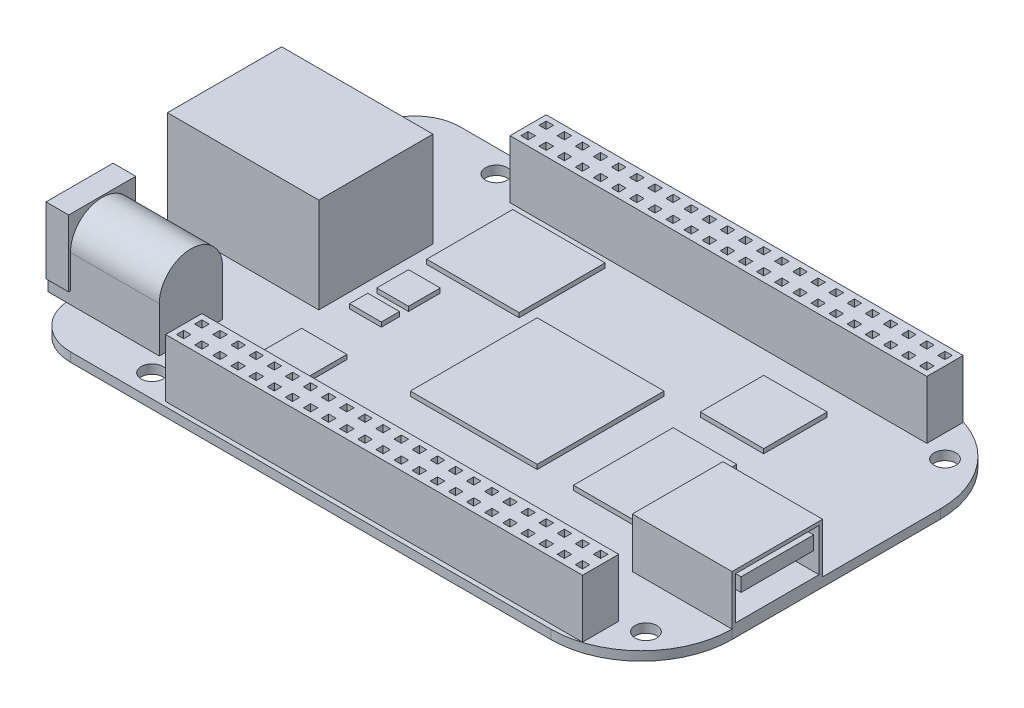
SolidWorks part; units mm, degrees
material "ABS"
ref_plane "Front Plane" through (0, 0, 0) normal (0, 0, 1) x (1, 0, 0)
ref_plane "Top Plane" through (0, 0, 0) normal (0, 1, 0) x (1, 0, 0)
ref_plane "Right Plane" through (0, 0, 0) normal (1, 0, 0) x (0, 0, -1)
sketch "Sketch1" plane through (0, 0, 0) normal (0, 1, 0) x (1, 0, 0)
  line L1 (-12.7, 0) -> (-80.01, 0)
  line L2 (0, 12.7) -> (0, 41.91)
  line L3 (-12.7, 54.61) -> (-80.01, 54.61)
  line L4 (-86.36, 6.35) -> (-86.36, 48.26)
  arc A0 (0, 12.7) -> (-12.7, 0) centre (-12.7, 12.7) cw
  arc A1 (0, 41.91) -> (-12.7, 54.61) centre (-12.7, 41.91) ccw
  arc A2 (-86.36, 6.35) -> (-80.01, 0) centre (-80.01, 6.35) ccw
  arc A3 (-86.36, 48.26) -> (-80.01, 54.61) centre (-80.01, 48.26) cw
  point P7 (0, 0)
  point P10 (0, 54.61)
  point P13 (-86.36, 0)
  dimension "D3" = 12.7
  dimension "D4" = 6.35
  dimension "D1" = 86.36
  dimension "D2" = 54.61
extrude "Boss-Extrude1" add sketch "Sketch1" along normal blind 1.27
sketch "Sketch2" plane through (0, 1.27, 0) normal (0, 1, 0) x (1, 0, 0)
  line L0 (-80.01, 0) -> (-12.7, 0) construction
  line L2 (-71.755, 51.435) -> (-71.755, 3.175) construction
  line L3 (-86.36, 48.26) -> (-86.36, 6.35) construction
  line L4 (-5.715, 48.26) -> (-5.715, 6.35) construction
  circle A0 centre (-71.755, 51.435) radius 1.524
  circle A1 centre (-71.755, 3.175) radius 1.524
  circle A2 centre (-5.715, 48.26) radius 1.524
  circle A3 centre (-5.715, 6.35) radius 1.524
  dimension "D7" = 3.048
  dimension "D1" = 48.26
  dimension "D2" = 41.91
  dimension "D3" = 6.35
  dimension "D4" = 14.605
  dimension "D5" = 80.645
  dimension "D6" = 3.175
extrude "Cut-Extrude1" cut sketch "Sketch2" along direction (0, -1, 0) on the side against the normal up to surface (1.27 mm away) up to face at (-44.4387, 0, -27.305)
sketch "Sketch3" plane through (0, 1.27, 0) normal (0, 1, 0) x (1, 0, 0)
  line L0 (-10.16, 48.895) -> (-10.16, 50.165) construction
  line L1 (-67.31, 53.975) -> (-8.89, 53.975)
  line L2 (-67.31, 53.975) -> (-67.31, 48.895)
  line L3 (-67.31, 48.895) -> (-8.89, 48.895)
  line L4 (-8.89, 53.975) -> (-8.89, 48.895)
  line L5 (-86.36, 27.305) -> (0, 27.305) construction
  line L6 (0, 12.7) -> (0, 41.91) construction
  line L7 (-66.548, 4.953) -> (-66.548, 3.937)
  line L8 (-66.548, 4.953) -> (-65.532, 4.953)
  line L9 (-10.16, 50.165) -> (-10.16, 52.705) construction
  line L10 (-10.16, 52.705) -> (-10.16, 53.975) construction
  line L11 (-13.208, 52.197) -> (-12.192, 52.197)
  line L12 (-10.668, 53.213) -> (-9.652, 53.213)
  line L13 (-10.668, 53.213) -> (-10.668, 52.197)
  line L14 (-10.668, 52.197) -> (-9.652, 52.197)
  line L15 (-9.652, 53.213) -> (-9.652, 52.197)
  line L16 (-10.668, 53.213) -> (-9.652, 52.197) construction
  line L17 (-10.668, 52.197) -> (-9.652, 53.213) construction
  line L18 (-10.668, 49.657) -> (-9.652, 49.657)
  line L19 (-10.668, 49.657) -> (-10.668, 50.673)
  line L20 (-10.668, 50.673) -> (-9.652, 50.673)
  line L21 (-9.652, 49.657) -> (-9.652, 50.673)
  line L22 (-10.668, 49.657) -> (-9.652, 50.673) construction
  line L23 (-10.668, 50.673) -> (-9.652, 49.657) construction
  line L24 (-13.208, 53.213) -> (-13.208, 52.197)
  line L25 (-13.208, 53.213) -> (-12.192, 53.213)
  line L26 (-12.192, 53.213) -> (-12.192, 52.197)
  line L27 (-13.208, 50.673) -> (-12.192, 50.673)
  line L28 (-12.192, 49.657) -> (-12.192, 50.673)
  line L29 (-13.208, 49.657) -> (-12.192, 49.657)
  line L30 (-13.208, 49.657) -> (-13.208, 50.673)
  line L31 (-15.748, 52.197) -> (-14.732, 52.197)
  line L32 (-15.748, 53.213) -> (-15.748, 52.197)
  line L33 (-15.748, 53.213) -> (-14.732, 53.213)
  line L34 (-14.732, 53.213) -> (-14.732, 52.197)
  line L35 (-15.748, 50.673) -> (-14.732, 50.673)
  line L36 (-14.732, 49.657) -> (-14.732, 50.673)
  line L37 (-15.748, 49.657) -> (-14.732, 49.657)
  line L38 (-15.748, 49.657) -> (-15.748, 50.673)
  line L39 (-18.288, 52.197) -> (-17.272, 52.197)
  line L40 (-18.288, 53.213) -> (-18.288, 52.197)
  line L41 (-18.288, 53.213) -> (-17.272, 53.213)
  line L42 (-17.272, 53.213) -> (-17.272, 52.197)
  line L43 (-18.288, 50.673) -> (-17.272, 50.673)
  line L44 (-17.272, 49.657) -> (-17.272, 50.673)
  line L45 (-18.288, 49.657) -> (-17.272, 49.657)
  line L46 (-18.288, 49.657) -> (-18.288, 50.673)
  line L47 (-20.828, 52.197) -> (-19.812, 52.197)
  line L48 (-20.828, 53.213) -> (-20.828, 52.197)
  line L49 (-20.828, 53.213) -> (-19.812, 53.213)
  line L50 (-19.812, 53.213) -> (-19.812, 52.197)
  line L51 (-20.828, 50.673) -> (-19.812, 50.673)
  line L52 (-19.812, 49.657) -> (-19.812, 50.673)
  line L53 (-20.828, 49.657) -> (-19.812, 49.657)
  line L54 (-20.828, 49.657) -> (-20.828, 50.673)
  line L55 (-23.368, 52.197) -> (-22.352, 52.197)
  line L56 (-23.368, 53.213) -> (-23.368, 52.197)
  line L57 (-23.368, 53.213) -> (-22.352, 53.213)
  line L58 (-22.352, 53.213) -> (-22.352, 52.197)
  line L59 (-23.368, 50.673) -> (-22.352, 50.673)
  line L60 (-22.352, 49.657) -> (-22.352, 50.673)
  line L61 (-23.368, 49.657) -> (-22.352, 49.657)
  line L62 (-23.368, 49.657) -> (-23.368, 50.673)
  line L63 (-25.908, 52.197) -> (-24.892, 52.197)
  line L64 (-25.908, 53.213) -> (-25.908, 52.197)
  line L65 (-25.908, 53.213) -> (-24.892, 53.213)
  line L66 (-24.892, 53.213) -> (-24.892, 52.197)
  line L67 (-25.908, 50.673) -> (-24.892, 50.673)
  line L68 (-24.892, 49.657) -> (-24.892, 50.673)
  line L69 (-25.908, 49.657) -> (-24.892, 49.657)
  line L70 (-25.908, 49.657) -> (-25.908, 50.673)
  line L71 (-28.448, 52.197) -> (-27.432, 52.197)
  line L72 (-28.448, 53.213) -> (-28.448, 52.197)
  line L73 (-28.448, 53.213) -> (-27.432, 53.213)
  line L74 (-27.432, 53.213) -> (-27.432, 52.197)
  line L75 (-28.448, 50.673) -> (-27.432, 50.673)
  line L76 (-27.432, 49.657) -> (-27.432, 50.673)
  line L77 (-28.448, 49.657) -> (-27.432, 49.657)
  line L78 (-28.448, 49.657) -> (-28.448, 50.673)
  line L79 (-30.988, 52.197) -> (-29.972, 52.197)
  line L80 (-30.988, 53.213) -> (-30.988, 52.197)
  line L81 (-30.988, 53.213) -> (-29.972, 53.213)
  line L82 (-29.972, 53.213) -> (-29.972, 52.197)
  line L83 (-30.988, 50.673) -> (-29.972, 50.673)
  line L84 (-29.972, 49.657) -> (-29.972, 50.673)
  line L85 (-30.988, 49.657) -> (-29.972, 49.657)
  line L86 (-30.988, 49.657) -> (-30.988, 50.673)
  line L87 (-33.528, 52.197) -> (-32.512, 52.197)
  line L88 (-33.528, 53.213) -> (-33.528, 52.197)
  line L89 (-33.528, 53.213) -> (-32.512, 53.213)
  line L90 (-32.512, 53.213) -> (-32.512, 52.197)
  line L91 (-33.528, 50.673) -> (-32.512, 50.673)
  line L92 (-32.512, 49.657) -> (-32.512, 50.673)
  line L93 (-33.528, 49.657) -> (-32.512, 49.657)
  line L94 (-33.528, 49.657) -> (-33.528, 50.673)
  line L95 (-36.068, 52.197) -> (-35.052, 52.197)
  line L96 (-36.068, 53.213) -> (-36.068, 52.197)
  line L97 (-36.068, 53.213) -> (-35.052, 53.213)
  line L98 (-35.052, 53.213) -> (-35.052, 52.197)
  line L99 (-36.068, 50.673) -> (-35.052, 50.673)
  line L100 (-35.052, 49.657) -> (-35.052, 50.673)
  line L101 (-36.068, 49.657) -> (-35.052, 49.657)
  line L102 (-36.068, 49.657) -> (-36.068, 50.673)
  line L103 (-38.608, 52.197) -> (-37.592, 52.197)
  line L104 (-38.608, 53.213) -> (-38.608, 52.197)
  line L105 (-38.608, 53.213) -> (-37.592, 53.213)
  line L106 (-37.592, 53.213) -> (-37.592, 52.197)
  line L107 (-38.608, 50.673) -> (-37.592, 50.673)
  line L108 (-37.592, 49.657) -> (-37.592, 50.673)
  line L109 (-38.608, 49.657) -> (-37.592, 49.657)
  line L110 (-38.608, 49.657) -> (-38.608, 50.673)
  line L111 (-41.148, 52.197) -> (-40.132, 52.197)
  line L112 (-41.148, 53.213) -> (-41.148, 52.197)
  line L113 (-41.148, 53.213) -> (-40.132, 53.213)
  line L114 (-40.132, 53.213) -> (-40.132, 52.197)
  line L115 (-41.148, 50.673) -> (-40.132, 50.673)
  line L116 (-40.132, 49.657) -> (-40.132, 50.673)
  line L117 (-41.148, 49.657) -> (-40.132, 49.657)
  line L118 (-41.148, 49.657) -> (-41.148, 50.673)
  line L119 (-43.688, 52.197) -> (-42.672, 52.197)
  line L120 (-43.688, 53.213) -> (-43.688, 52.197)
  line L121 (-43.688, 53.213) -> (-42.672, 53.213)
  line L122 (-42.672, 53.213) -> (-42.672, 52.197)
  line L123 (-43.688, 50.673) -> (-42.672, 50.673)
  line L124 (-42.672, 49.657) -> (-42.672, 50.673)
  line L125 (-43.688, 49.657) -> (-42.672, 49.657)
  line L126 (-43.688, 49.657) -> (-43.688, 50.673)
  line L127 (-46.228, 52.197) -> (-45.212, 52.197)
  line L128 (-46.228, 53.213) -> (-46.228, 52.197)
  line L129 (-46.228, 53.213) -> (-45.212, 53.213)
  line L130 (-45.212, 53.213) -> (-45.212, 52.197)
  line L131 (-46.228, 50.673) -> (-45.212, 50.673)
  line L132 (-45.212, 49.657) -> (-45.212, 50.673)
  line L133 (-46.228, 49.657) -> (-45.212, 49.657)
  line L134 (-46.228, 49.657) -> (-46.228, 50.673)
  line L135 (-48.768, 52.197) -> (-47.752, 52.197)
  line L136 (-48.768, 53.213) -> (-48.768, 52.197)
  line L137 (-48.768, 53.213) -> (-47.752, 53.213)
  line L138 (-47.752, 53.213) -> (-47.752, 52.197)
  line L139 (-48.768, 50.673) -> (-47.752, 50.673)
  line L140 (-47.752, 49.657) -> (-47.752, 50.673)
  line L141 (-48.768, 49.657) -> (-47.752, 49.657)
  line L142 (-48.768, 49.657) -> (-48.768, 50.673)
  line L143 (-51.308, 52.197) -> (-50.292, 52.197)
  line L144 (-51.308, 53.213) -> (-51.308, 52.197)
  line L145 (-51.308, 53.213) -> (-50.292, 53.213)
  line L146 (-50.292, 53.213) -> (-50.292, 52.197)
  line L147 (-51.308, 50.673) -> (-50.292, 50.673)
  line L148 (-50.292, 49.657) -> (-50.292, 50.673)
  line L149 (-51.308, 49.657) -> (-50.292, 49.657)
  line L150 (-51.308, 49.657) -> (-51.308, 50.673)
  line L151 (-53.848, 52.197) -> (-52.832, 52.197)
  line L152 (-53.848, 53.213) -> (-53.848, 52.197)
  line L153 (-53.848, 53.213) -> (-52.832, 53.213)
  line L154 (-52.832, 53.213) -> (-52.832, 52.197)
  line L155 (-53.848, 50.673) -> (-52.832, 50.673)
  line L156 (-52.832, 49.657) -> (-52.832, 50.673)
  line L157 (-53.848, 49.657) -> (-52.832, 49.657)
  line L158 (-53.848, 49.657) -> (-53.848, 50.673)
  line L159 (-56.388, 52.197) -> (-55.372, 52.197)
  line L160 (-56.388, 53.213) -> (-56.388, 52.197)
  line L161 (-56.388, 53.213) -> (-55.372, 53.213)
  line L162 (-55.372, 53.213) -> (-55.372, 52.197)
  line L163 (-56.388, 50.673) -> (-55.372, 50.673)
  line L164 (-55.372, 49.657) -> (-55.372, 50.673)
  line L165 (-56.388, 49.657) -> (-55.372, 49.657)
  line L166 (-56.388, 49.657) -> (-56.388, 50.673)
  line L167 (-58.928, 52.197) -> (-57.912, 52.197)
  line L168 (-58.928, 53.213) -> (-58.928, 52.197)
  line L169 (-58.928, 53.213) -> (-57.912, 53.213)
  line L170 (-57.912, 53.213) -> (-57.912, 52.197)
  line L171 (-58.928, 50.673) -> (-57.912, 50.673)
  line L172 (-57.912, 49.657) -> (-57.912, 50.673)
  line L173 (-58.928, 49.657) -> (-57.912, 49.657)
  line L174 (-58.928, 49.657) -> (-58.928, 50.673)
  line L175 (-61.468, 52.197) -> (-60.452, 52.197)
  line L176 (-61.468, 53.213) -> (-61.468, 52.197)
  line L177 (-61.468, 53.213) -> (-60.452, 53.213)
  line L178 (-60.452, 53.213) -> (-60.452, 52.197)
  line L179 (-61.468, 50.673) -> (-60.452, 50.673)
  line L180 (-60.452, 49.657) -> (-60.452, 50.673)
  line L181 (-61.468, 49.657) -> (-60.452, 49.657)
  line L182 (-61.468, 49.657) -> (-61.468, 50.673)
  line L183 (-64.008, 52.197) -> (-62.992, 52.197)
  line L184 (-64.008, 53.213) -> (-64.008, 52.197)
  line L185 (-64.008, 53.213) -> (-62.992, 53.213)
  line L186 (-62.992, 53.213) -> (-62.992, 52.197)
  line L187 (-64.008, 50.673) -> (-62.992, 50.673)
  line L188 (-62.992, 49.657) -> (-62.992, 50.673)
  line L189 (-64.008, 49.657) -> (-62.992, 49.657)
  line L190 (-64.008, 49.657) -> (-64.008, 50.673)
  line L191 (-66.548, 52.197) -> (-65.532, 52.197)
  line L192 (-66.548, 53.213) -> (-66.548, 52.197)
  line L193 (-66.548, 53.213) -> (-65.532, 53.213)
  line L194 (-65.532, 53.213) -> (-65.532, 52.197)
  line L195 (-66.548, 50.673) -> (-65.532, 50.673)
  line L196 (-65.532, 49.657) -> (-65.532, 50.673)
  line L197 (-66.548, 49.657) -> (-65.532, 49.657)
  line L198 (-66.548, 49.657) -> (-66.548, 50.673)
  line L199 (-66.548, 49.657) -> (-65.532, 50.673) construction
  line L200 (-86.36, 48.26) -> (-86.36, 6.35) construction
  line L201 (-65.532, 4.953) -> (-65.532, 3.937)
  line L202 (-12.7, 54.61) -> (-80.01, 54.61) construction
  line L203 (-66.548, 3.937) -> (-65.532, 3.937)
  line L204 (-65.532, 1.397) -> (-65.532, 2.413)
  line L205 (-66.548, 1.397) -> (-65.532, 1.397)
  line L206 (-66.548, 1.397) -> (-66.548, 2.413)
  line L207 (-66.548, 2.413) -> (-65.532, 2.413)
  line L208 (-64.008, 4.953) -> (-64.008, 3.937)
  line L209 (-64.008, 4.953) -> (-62.992, 4.953)
  line L210 (-62.992, 4.953) -> (-62.992, 3.937)
  line L211 (-64.008, 3.937) -> (-62.992, 3.937)
  line L212 (-62.992, 1.397) -> (-62.992, 2.413)
  line L213 (-64.008, 1.397) -> (-62.992, 1.397)
  line L214 (-64.008, 1.397) -> (-64.008, 2.413)
  line L215 (-64.008, 2.413) -> (-62.992, 2.413)
  line L216 (-61.468, 4.953) -> (-61.468, 3.937)
  line L217 (-61.468, 4.953) -> (-60.452, 4.953)
  line L218 (-60.452, 4.953) -> (-60.452, 3.937)
  line L219 (-61.468, 3.937) -> (-60.452, 3.937)
  line L220 (-60.452, 1.397) -> (-60.452, 2.413)
  line L221 (-61.468, 1.397) -> (-60.452, 1.397)
  line L222 (-61.468, 1.397) -> (-61.468, 2.413)
  line L223 (-61.468, 2.413) -> (-60.452, 2.413)
  line L224 (-58.928, 4.953) -> (-58.928, 3.937)
  line L225 (-58.928, 4.953) -> (-57.912, 4.953)
  line L226 (-57.912, 4.953) -> (-57.912, 3.937)
  line L227 (-58.928, 3.937) -> (-57.912, 3.937)
  line L228 (-57.912, 1.397) -> (-57.912, 2.413)
  line L229 (-58.928, 1.397) -> (-57.912, 1.397)
  line L230 (-58.928, 1.397) -> (-58.928, 2.413)
  line L231 (-58.928, 2.413) -> (-57.912, 2.413)
  line L232 (-56.388, 4.953) -> (-56.388, 3.937)
  line L233 (-56.388, 4.953) -> (-55.372, 4.953)
  line L234 (-55.372, 4.953) -> (-55.372, 3.937)
  line L235 (-56.388, 3.937) -> (-55.372, 3.937)
  line L236 (-55.372, 1.397) -> (-55.372, 2.413)
  line L237 (-56.388, 1.397) -> (-55.372, 1.397)
  line L238 (-56.388, 1.397) -> (-56.388, 2.413)
  line L239 (-56.388, 2.413) -> (-55.372, 2.413)
  line L240 (-53.848, 4.953) -> (-53.848, 3.937)
  line L241 (-53.848, 4.953) -> (-52.832, 4.953)
  line L242 (-52.832, 4.953) -> (-52.832, 3.937)
  line L243 (-53.848, 3.937) -> (-52.832, 3.937)
  line L244 (-52.832, 1.397) -> (-52.832, 2.413)
  line L245 (-53.848, 1.397) -> (-52.832, 1.397)
  line L246 (-53.848, 1.397) -> (-53.848, 2.413)
  line L247 (-53.848, 2.413) -> (-52.832, 2.413)
  line L248 (-51.308, 4.953) -> (-51.308, 3.937)
  line L249 (-51.308, 4.953) -> (-50.292, 4.953)
  line L250 (-50.292, 4.953) -> (-50.292, 3.937)
  line L251 (-51.308, 3.937) -> (-50.292, 3.937)
  line L252 (-50.292, 1.397) -> (-50.292, 2.413)
  line L253 (-51.308, 1.397) -> (-50.292, 1.397)
  line L254 (-51.308, 1.397) -> (-51.308, 2.413)
  line L255 (-51.308, 2.413) -> (-50.292, 2.413)
  line L256 (-48.768, 4.953) -> (-48.768, 3.937)
  line L257 (-48.768, 4.953) -> (-47.752, 4.953)
  line L258 (-47.752, 4.953) -> (-47.752, 3.937)
  line L259 (-48.768, 3.937) -> (-47.752, 3.937)
  line L260 (-47.752, 1.397) -> (-47.752, 2.413)
  line L261 (-48.768, 1.397) -> (-47.752, 1.397)
  line L262 (-48.768, 1.397) -> (-48.768, 2.413)
  line L263 (-48.768, 2.413) -> (-47.752, 2.413)
  line L264 (-46.228, 4.953) -> (-46.228, 3.937)
  line L265 (-46.228, 4.953) -> (-45.212, 4.953)
  line L266 (-45.212, 4.953) -> (-45.212, 3.937)
  line L267 (-46.228, 3.937) -> (-45.212, 3.937)
  line L268 (-45.212, 1.397) -> (-45.212, 2.413)
  line L269 (-46.228, 1.397) -> (-45.212, 1.397)
  line L270 (-46.228, 1.397) -> (-46.228, 2.413)
  line L271 (-46.228, 2.413) -> (-45.212, 2.413)
  line L272 (-43.688, 4.953) -> (-43.688, 3.937)
  line L273 (-43.688, 4.953) -> (-42.672, 4.953)
  line L274 (-42.672, 4.953) -> (-42.672, 3.937)
  line L275 (-43.688, 3.937) -> (-42.672, 3.937)
  line L276 (-42.672, 1.397) -> (-42.672, 2.413)
  line L277 (-43.688, 1.397) -> (-42.672, 1.397)
  line L278 (-43.688, 1.397) -> (-43.688, 2.413)
  line L279 (-43.688, 2.413) -> (-42.672, 2.413)
  line L280 (-41.148, 4.953) -> (-41.148, 3.937)
  line L281 (-41.148, 4.953) -> (-40.132, 4.953)
  line L282 (-40.132, 4.953) -> (-40.132, 3.937)
  line L283 (-41.148, 3.937) -> (-40.132, 3.937)
  line L284 (-40.132, 1.397) -> (-40.132, 2.413)
  line L285 (-41.148, 1.397) -> (-40.132, 1.397)
  line L286 (-41.148, 1.397) -> (-41.148, 2.413)
  line L287 (-41.148, 2.413) -> (-40.132, 2.413)
  line L288 (-38.608, 4.953) -> (-38.608, 3.937)
  line L289 (-38.608, 4.953) -> (-37.592, 4.953)
  line L290 (-37.592, 4.953) -> (-37.592, 3.937)
  line L291 (-38.608, 3.937) -> (-37.592, 3.937)
  line L292 (-37.592, 1.397) -> (-37.592, 2.413)
  line L293 (-38.608, 1.397) -> (-37.592, 1.397)
  line L294 (-38.608, 1.397) -> (-38.608, 2.413)
  line L295 (-38.608, 2.413) -> (-37.592, 2.413)
  line L296 (-36.068, 4.953) -> (-36.068, 3.937)
  line L297 (-36.068, 4.953) -> (-35.052, 4.953)
  line L298 (-35.052, 4.953) -> (-35.052, 3.937)
  line L299 (-36.068, 3.937) -> (-35.052, 3.937)
  line L300 (-35.052, 1.397) -> (-35.052, 2.413)
  line L301 (-36.068, 1.397) -> (-35.052, 1.397)
  line L302 (-36.068, 1.397) -> (-36.068, 2.413)
  line L303 (-36.068, 2.413) -> (-35.052, 2.413)
  line L304 (-33.528, 4.953) -> (-33.528, 3.937)
  line L305 (-33.528, 4.953) -> (-32.512, 4.953)
  line L306 (-32.512, 4.953) -> (-32.512, 3.937)
  line L307 (-33.528, 3.937) -> (-32.512, 3.937)
  line L308 (-32.512, 1.397) -> (-32.512, 2.413)
  line L309 (-33.528, 1.397) -> (-32.512, 1.397)
  line L310 (-33.528, 1.397) -> (-33.528, 2.413)
  line L311 (-33.528, 2.413) -> (-32.512, 2.413)
  line L312 (-30.988, 4.953) -> (-30.988, 3.937)
  line L313 (-30.988, 4.953) -> (-29.972, 4.953)
  line L314 (-29.972, 4.953) -> (-29.972, 3.937)
  line L315 (-30.988, 3.937) -> (-29.972, 3.937)
  line L316 (-29.972, 1.397) -> (-29.972, 2.413)
  line L317 (-30.988, 1.397) -> (-29.972, 1.397)
  line L318 (-30.988, 1.397) -> (-30.988, 2.413)
  line L319 (-30.988, 2.413) -> (-29.972, 2.413)
  line L320 (-28.448, 4.953) -> (-28.448, 3.937)
  line L321 (-28.448, 4.953) -> (-27.432, 4.953)
  line L322 (-27.432, 4.953) -> (-27.432, 3.937)
  line L323 (-28.448, 3.937) -> (-27.432, 3.937)
  line L324 (-27.432, 1.397) -> (-27.432, 2.413)
  line L325 (-28.448, 1.397) -> (-27.432, 1.397)
  line L326 (-28.448, 1.397) -> (-28.448, 2.413)
  line L327 (-28.448, 2.413) -> (-27.432, 2.413)
  line L328 (-25.908, 4.953) -> (-25.908, 3.937)
  line L329 (-25.908, 4.953) -> (-24.892, 4.953)
  line L330 (-24.892, 4.953) -> (-24.892, 3.937)
  line L331 (-25.908, 3.937) -> (-24.892, 3.937)
  line L332 (-24.892, 1.397) -> (-24.892, 2.413)
  line L333 (-25.908, 1.397) -> (-24.892, 1.397)
  line L334 (-25.908, 1.397) -> (-25.908, 2.413)
  line L335 (-25.908, 2.413) -> (-24.892, 2.413)
  line L336 (-23.368, 4.953) -> (-23.368, 3.937)
  line L337 (-23.368, 4.953) -> (-22.352, 4.953)
  line L338 (-22.352, 4.953) -> (-22.352, 3.937)
  line L339 (-23.368, 3.937) -> (-22.352, 3.937)
  line L340 (-22.352, 1.397) -> (-22.352, 2.413)
  line L341 (-23.368, 1.397) -> (-22.352, 1.397)
  line L342 (-23.368, 1.397) -> (-23.368, 2.413)
  line L343 (-23.368, 2.413) -> (-22.352, 2.413)
  line L344 (-20.828, 4.953) -> (-20.828, 3.937)
  line L345 (-20.828, 4.953) -> (-19.812, 4.953)
  line L346 (-19.812, 4.953) -> (-19.812, 3.937)
  line L347 (-20.828, 3.937) -> (-19.812, 3.937)
  line L348 (-19.812, 1.397) -> (-19.812, 2.413)
  line L349 (-20.828, 1.397) -> (-19.812, 1.397)
  line L350 (-20.828, 1.397) -> (-20.828, 2.413)
  line L351 (-20.828, 2.413) -> (-19.812, 2.413)
  line L352 (-18.288, 4.953) -> (-18.288, 3.937)
  line L353 (-18.288, 4.953) -> (-17.272, 4.953)
  line L354 (-17.272, 4.953) -> (-17.272, 3.937)
  line L355 (-18.288, 3.937) -> (-17.272, 3.937)
  line L356 (-17.272, 1.397) -> (-17.272, 2.413)
  line L357 (-18.288, 1.397) -> (-17.272, 1.397)
  line L358 (-18.288, 1.397) -> (-18.288, 2.413)
  line L359 (-18.288, 2.413) -> (-17.272, 2.413)
  line L360 (-15.748, 4.953) -> (-15.748, 3.937)
  line L361 (-15.748, 4.953) -> (-14.732, 4.953)
  line L362 (-14.732, 4.953) -> (-14.732, 3.937)
  line L363 (-15.748, 3.937) -> (-14.732, 3.937)
  line L364 (-14.732, 1.397) -> (-14.732, 2.413)
  line L365 (-15.748, 1.397) -> (-14.732, 1.397)
  line L366 (-15.748, 1.397) -> (-15.748, 2.413)
  line L367 (-15.748, 2.413) -> (-14.732, 2.413)
  line L368 (-13.208, 4.953) -> (-13.208, 3.937)
  line L369 (-13.208, 4.953) -> (-12.192, 4.953)
  line L370 (-12.192, 4.953) -> (-12.192, 3.937)
  line L371 (-13.208, 3.937) -> (-12.192, 3.937)
  line L372 (-12.192, 1.397) -> (-12.192, 2.413)
  line L373 (-13.208, 1.397) -> (-12.192, 1.397)
  line L374 (-13.208, 1.397) -> (-13.208, 2.413)
  line L375 (-9.652, 4.953) -> (-9.652, 3.937)
  line L376 (-10.668, 3.937) -> (-9.652, 3.937)
  line L377 (-10.668, 4.953) -> (-10.668, 3.937)
  line L378 (-10.668, 4.953) -> (-9.652, 4.953)
  line L379 (-9.652, 1.397) -> (-9.652, 2.413)
  line L380 (-10.668, 2.413) -> (-9.652, 2.413)
  line L381 (-10.668, 1.397) -> (-10.668, 2.413)
  line L382 (-10.668, 1.397) -> (-9.652, 1.397)
  line L383 (-13.208, 2.413) -> (-12.192, 2.413)
  line L384 (-8.89, 0.635) -> (-8.89, 5.715)
  line L385 (-67.31, 5.715) -> (-8.89, 5.715)
  line L386 (-67.31, 0.635) -> (-67.31, 5.715)
  line L387 (-67.31, 0.635) -> (-8.89, 0.635)
  circle A0 centre (-66.04, 50.165) radius 0.1361
  dimension "D1" = 1.016
  dimension "D2" = 2.54
  dimension "D3" = 5.08
  dimension "D4" = 58.42
  dimension "D5" = 1.27
  dimension "D7" = 20.32
  dimension "D8" = 0.635
  dimension "D6" = 23
extrude "Boss-Extrude2" add sketch "Sketch3" along normal blind 8.128 contours L4 L1 L2 L3 L193 L194 L191 L192 L185 L186 L183 L184 L177 L178 L175 L176 L169 L170 L167 L168 L161 L162 L159 L160 L153 L154 L151 L152 L145 L146 L143 L144 L137 L138 L135 L136 L129 L130 L127 L128 L121 | L386 L387 L384 L385 L374 L383 L372 L373 L382 L381 L380 L379 L366 L367 L364 L365 L363 L360 L361 L362 L350 L351 L348 L349 L347 L344 L345 L346 L334 L335 L332 L333 L331 L328 L329 L330 L318 L319 L316 L317 L315 region at (-38.1, 1.27, -51.435) region at (-38.1, 1.27, -3.175)
sketch "Sketch4" plane through (0, 1.27, 0) normal (0, 1, 0) x (1, 0, 0)
  line L0 (-86.36, 48.26) -> (-86.36, 6.35) construction
  line L1 (-67.691, 22.479) -> (-88.9, 22.479)
  line L2 (-67.691, 22.479) -> (-67.691, 38.481)
  line L3 (-67.691, 38.481) -> (-88.9, 38.481)
  line L4 (-88.9, 22.479) -> (-88.9, 38.481)
  line L5 (-12.7, 54.61) -> (-80.01, 54.61) construction
  dimension "D1" = 2.54
  dimension "D2" = 21.209
  dimension "D3" = 16.002
  dimension "D4" = 16.129
extrude "Boss-Extrude3" add sketch "Sketch4" along normal blind 13.335
sketch "Sketch5" plane through (-88.9, 0, 0) normal (-1, 0, 0) x (0, 0, 1)
  line L0 (-30.48, 2.286) -> (-30.48, 3.937) construction
  line L1 (-36.83, 12.065) -> (-24.13, 12.065)
  line L2 (-36.83, 12.065) -> (-36.83, 5.461)
  line L3 (-36.83, 5.461) -> (-24.13, 5.461)
  line L4 (-24.13, 12.065) -> (-24.13, 5.461)
  line L5 (-33.655, 5.461) -> (-27.305, 5.461)
  line L6 (-33.655, 5.461) -> (-33.655, 3.937)
  line L7 (-33.655, 3.937) -> (-27.305, 3.937)
  line L8 (-27.305, 5.461) -> (-27.305, 3.937)
  line L9 (-32.512, 3.937) -> (-28.448, 3.937)
  line L10 (-32.512, 3.937) -> (-32.512, 2.286)
  line L11 (-32.512, 2.286) -> (-28.448, 2.286)
  line L12 (-28.448, 3.937) -> (-28.448, 2.286)
  line L13 (-30.48, 3.937) -> (-30.48, 5.461) construction
  line L14 (-38.481, 14.605) -> (-22.479, 14.605) construction
  line L15 (-36.83, 12.065) -> (-38.481, 12.065) construction
  line L16 (-38.481, 14.605) -> (-38.481, 1.27) construction
  line L17 (-24.13, 12.065) -> (-22.479, 12.065) construction
  line L18 (-22.479, 14.605) -> (-22.479, 1.27) construction
  dimension "D1" = 12.7
  dimension "D2" = 6.604
  dimension "D3" = 2.54
  dimension "D4" = 1.524
  dimension "D5" = 1.651
  dimension "D6" = 4.064
  dimension "D7" = 6.35
extrude "Cut-Extrude2" cut sketch "Sketch5" against normal blind 17.78 contours L4 L1 L2 L3 | L8 L3 L6 L7 | L12 L7 L10 L11 region at (-88.9, 8.763, -30.48) region at (-88.9, 4.699, -30.48) region at (-88.9, 3.1115, -30.48)
sketch "Sketch6" plane through (0, 1.27, 0) normal (0, 1, 0) x (1, 0, 0)
  line L0 (-67.31, 48.895) -> (-8.89, 48.895) construction
  line L1 (-65.659, 35.56) -> (-52.705, 35.56)
  line L2 (-65.659, 35.56) -> (-65.659, 47.625)
  line L3 (-65.659, 47.625) -> (-52.705, 47.625)
  line L4 (-52.705, 35.56) -> (-52.705, 47.625)
  line L5 (-50.8, 36.195) -> (-33.02, 36.195)
  line L6 (-50.8, 36.195) -> (-50.8, 18.415)
  line L7 (-50.8, 18.415) -> (-33.02, 18.415)
  line L8 (-33.02, 36.195) -> (-33.02, 18.415)
  line L9 (-27.94, 45.085) -> (-19.05, 45.085)
  line L10 (-27.94, 45.085) -> (-27.94, 36.195)
  line L11 (-27.94, 36.195) -> (-19.05, 36.195)
  line L12 (-19.05, 45.085) -> (-19.05, 36.195)
  line L13 (-27.94, 32.385) -> (-19.05, 32.385)
  line L14 (-27.94, 32.385) -> (-27.94, 18.415)
  line L15 (-27.94, 18.415) -> (-19.05, 18.415)
  line L16 (-19.05, 32.385) -> (-19.05, 18.415)
  line L17 (-66.04, 18.415) -> (-59.69, 18.415)
  line L18 (-66.04, 18.415) -> (-66.04, 12.065)
  line L19 (-66.04, 12.065) -> (-59.69, 12.065)
  line L20 (-59.69, 18.415) -> (-59.69, 12.065)
  line L21 (-65.659, 27.305) -> (-61.214, 27.305)
  line L22 (-65.659, 27.305) -> (-65.659, 24.765)
  line L23 (-65.659, 24.765) -> (-61.214, 24.765)
  line L24 (-61.214, 27.305) -> (-61.214, 24.765)
  line L25 (-65.659, 33.02) -> (-61.214, 33.02)
  line L26 (-65.659, 33.02) -> (-65.659, 28.575)
  line L27 (-65.659, 28.575) -> (-61.214, 28.575)
  line L28 (-61.214, 33.02) -> (-61.214, 28.575)
  line L29 (0, 12.7) -> (0, 41.91) construction
  line L30 (-67.31, 48.895) -> (-8.89, 48.895) construction
  line L31 (-67.31, 5.715) -> (-8.89, 5.715) construction
  line L33 (-67.31, 0.635) -> (-67.31, 5.715) construction
  dimension "D1" = 8.89
  dimension "D2" = 13.97
  dimension "D3" = 3.81
  dimension "D4" = 3.81
  dimension "D5" = 19.05
  dimension "D6" = 17.78
  dimension "D7" = 12.7
  dimension "D8" = 33.02
  dimension "D9" = 12.954
  dimension "D10" = 12.065
  dimension "D11" = 1.905
  dimension "D12" = 4.445
  dimension "D13" = 2.54
  dimension "D14" = 1.27
  dimension "D15" = 2.54
  dimension "D16" = 1.27
  dimension "D17" = 6.35
  dimension "D18" = 6.35
  dimension "D19" = 1.27
extrude "Boss-Extrude4" add sketch "Sketch6" along normal blind 0.635
sketch "Sketch7" plane through (0, 1.27, 0) normal (0, 1, 0) x (1, 0, 0)
  line L1 (0, 12.7) -> (-13.97, 12.7)
  line L2 (0, 12.7) -> (0, 25.4)
  line L3 (0, 25.4) -> (-13.97, 25.4)
  line L4 (-13.97, 12.7) -> (-13.97, 25.4)
  line L5 (-80.01, 0) -> (-12.7, 0) construction
  line L6 (0, 12.7) -> (0, 41.91) construction
  dimension "D1" = 12.7
  dimension "D2" = 13.97
  dimension "D3" = 25.4
extrude "Boss-Extrude5" add sketch "Sketch7" along normal blind 6.985
sketch "Sketch8" plane through (0, 0, 0) normal (1, 0, 0) x (0, 0, -1)
  line L0 (12.7, 8.255) -> (25.4, 8.255) construction
  line L1 (13.97, 6.985) -> (24.13, 6.985)
  line L2 (13.97, 6.985) -> (13.97, 5.08)
  line L3 (13.97, 5.08) -> (24.13, 5.08)
  line L4 (24.13, 6.985) -> (24.13, 5.08)
  line L5 (13.208, 7.747) -> (24.892, 7.747)
  line L6 (13.208, 7.747) -> (13.208, 1.778)
  line L7 (13.208, 1.778) -> (24.892, 1.778)
  line L8 (24.892, 7.747) -> (24.892, 1.778)
  line L9 (25.4, 8.255) -> (25.4, 1.27) construction
  line L10 (12.7, 8.255) -> (12.7, 1.27) construction
  line L11 (12.7, 1.27) -> (0, 1.27) construction
  line L12 (13.97, 7.18) -> (13.208, 7.18) construction
  line L14 (24.892, 6.9479) -> (24.13, 6.9479) construction
  dimension "D1" = 0.508
  dimension "D2" = 0.508
  dimension "D3" = 0.508
  dimension "D4" = 0.508
  dimension "D5" = 1.905
  dimension "D6" = 10.16
  dimension "D7" = 3.175
extrude "Cut-Extrude3" cut sketch "Sketch8" against normal blind 12.7
sketch "Sketch9" plane through (0, 1.27, 0) normal (0, 1, 0) x (1, 0, 0)
  line L0 (-88.9, 38.481) -> (-88.9, 22.479) construction
  line L1 (-73.279, 5.715) -> (-88.9, 5.715)
  line L2 (-73.279, 5.715) -> (-73.279, 14.605)
  line L3 (-73.279, 14.605) -> (-88.9, 14.605)
  line L4 (-88.9, 5.715) -> (-88.9, 14.605)
  line L5 (-67.31, 5.715) -> (-8.89, 5.715) construction
  circle A0 centre (-71.755, 3.175) radius 1.524 construction
  dimension "D1" = 8.89
extrude "Boss-Extrude6" add sketch "Sketch9" along normal blind 6.35
sketch "Sketch10" plane through (-88.9, 0, 0) normal (-1, 0, 0) x (0, 0, 1)
  line L0 (-14.605, 7.62) -> (-5.715, 7.62) construction
  circle A0 centre (-10.16, 7.62) radius 4.445
  circle A1 centre (-10.16, 7.62) radius 3.4925
  circle A2 centre (-10.16, 7.62) radius 0.635
  line M3 (-5.715, 7.62) -> (-14.605, 7.62)
  dimension "D1" = 1.27
  dimension "D2" = 6.985
extrude "Boss-Extrude7" add sketch "Sketch10" along direction (1, 0, 0) on the side against the normal up to surface (15.621 mm away) contours A1 A0 M3 | A1 A0 M3 | A2 M3 | A2 A1 M3 region at (-88.9, 7.7194, -6.1912) region at (-88.9, 3.2744, -10.16) region at (-88.9, 9.1437, -10.16) region at (-88.9, 7.8895, -10.16) up to face at (-73.279, 4.445, -10.16)
sketch "Sketch11" plane through (-88.9, 0, 0) normal (-1, 0, 0) x (0, 0, 1)
  line L0 (-14.605, 7.62) -> (-14.605, 1.27) construction
  line L1 (-5.461, 2.952) -> (-14.859, 2.952)
  line L2 (-5.461, 2.952) -> (-5.461, 12.288)
  line L3 (-5.461, 12.288) -> (-14.859, 12.288)
  line L4 (-14.859, 2.952) -> (-14.859, 12.288)
  line L5 (-5.461, 2.952) -> (-14.859, 12.288) construction
  line L6 (-5.461, 12.288) -> (-14.859, 2.952) construction
  point P0 (-10.16, 7.62)
  dimension "D1" = 0.254
extrude "Boss-Extrude8" add sketch "Sketch11" against normal blind 3.175
extrude "Cut-Extrude4" cut sketch "Sketch10<3>" against normal blind 12.7 contours A2 A1 M3 | A2 A1 M3 region at (-88.9, 9.1437, -10.16) region at (-88.9, 6.0963, -10.16)
sketch "Sketch10<3>" plane through (-88.9, 0, 0) normal (-1, 0, 0) x (0, 0, 1) same geometry as "Sketch10"
fillet "Fillet1" radius 0.635 1 edges at (-88.9, 7.62, -9.525)
